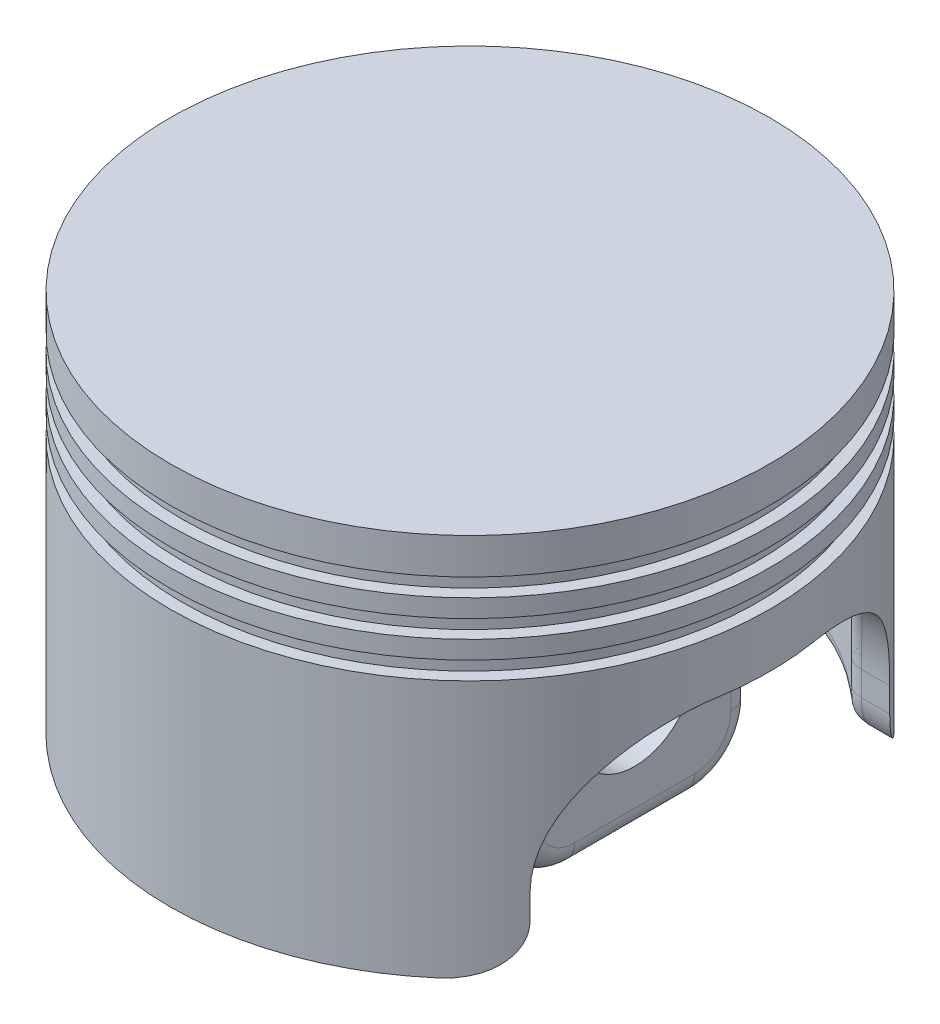
SolidWorks part; units mm, degrees
ref_plane "Front Plane" through (0, 0, 0) normal (0, 0, 1) x (1, 0, 0)
ref_plane "Top Plane" through (0, 0, 0) normal (0, 1, 0) x (1, 0, 0)
ref_plane "Right Plane" through (0, 0, 0) normal (1, 0, 0) x (0, 0, -1)
sketch "Sketch1" plane through (0, 0, 0) normal (1, 0, 0) x (0, 0, -1)
  line L0 (0, 0) -> (63.5, 0)
  line L4 (57.15, -19) -> (0, -19)
  line L5 (0, -19) -> (0, 0)
  line L6 (63.5, 0) -> (63.5, -81.28)
  line L7 (63.5, -81.28) -> (57.15, -81.28)
  line L8 (57.15, -81.28) -> (57.15, -19)
  dimension "D1" = 19
  dimension "D2" = 63.5
  dimension "D3" = 6.35
  dimension "D4" = 81.28
revolve "Revolve1" add sketch "Sketch1" angle 360 about L5
sketch "Sketch2" plane through (0, 0, 0) normal (0, 0, 1) x (1, 0, 0)
  line L0 (63.5, 0) -> (-63.5, 0) construction
  line L1 (63.5, -7.62) -> (60.96, -7.62)
  line L2 (63.5, -7.62) -> (63.5, -11.43)
  line L3 (63.5, -11.43) -> (60.96, -11.43)
  line L4 (60.96, -7.62) -> (60.96, -11.43)
  line L5 (63.5, -7.62) -> (60.96, -11.43) construction
  line L6 (63.5, -11.43) -> (60.96, -7.62) construction
  point P0 (62.23, -9.525)
  dimension "D1" = 7.62
  dimension "D2" = 3.81
  dimension "D3" = 2.54
  dimension "D4" = 63.5
ref_axis "Axis1" through (0, 4.064, 0) along (0, -1, 0)
revolve "Cut-Revolve1" cut sketch "Sketch2" angle 360 about axis through (0, 4.064, 0) along (0, -1, 0)
pattern_linear "LPattern1" count 3 spacing 7.62 along (0, -1, 0) of "Cut-Revolve1"
sketch "Sketch4" plane through (0, 0, 0) normal (1, 0, 0) x (0, 0, -1)
  line L0 (-57.15, -81.28) -> (57.15, -81.28) construction
  line L1 (-38.1, -38.1) -> (38.1, -38.1)
  line L2 (-38.1, -38.1) -> (-38.1, -81.28)
  line L3 (-38.1, -81.28) -> (38.1, -81.28)
  line L4 (38.1, -38.1) -> (38.1, -81.28)
  line L5 (-38.1, -38.1) -> (38.1, -81.28) construction
  line L6 (-38.1, -81.28) -> (38.1, -38.1) construction
  line L7 (63.5, 0) -> (-63.5, 0) construction
  point P0 (0, -59.69)
  dimension "D1" = 76.2
  dimension "D2" = 38.1
extrude "Cut-Extrude1" cut sketch "Sketch4" against normal mid plane 166
fillet "Fillet1" radius 28 4 edges at (-46.6985, -38.1, -38.1) (-46.6985, -38.1, 38.1) (46.6985, -38.1, -38.1) (46.6985, -38.1, 38.1)
sketch "Sketch5" plane through (0, -19, 0) normal (0, -1, 0) x (1, 0, 0)
  line L1 (-34.88, 25.4) -> (-15.88, 25.4)
  line L2 (-34.88, 25.4) -> (-34.88, -25.4)
  line L3 (-34.88, -25.4) -> (-15.88, -25.4)
  line L4 (-15.88, 25.4) -> (-15.88, -25.4)
  line L5 (-34.88, 25.4) -> (-15.88, -25.4) construction
  line L6 (-34.88, -25.4) -> (-15.88, 25.4) construction
  point P0 (-25.38, 0)
  dimension "D1" = 15.88
  dimension "D2" = 50.8
  dimension "D3" = 19
extrude "Boss-Extrude1" add sketch "Sketch5" along normal blind 63.5
mirror "Mirror1" about plane through (0, 0, 0) normal (1, 0, 0) of "Boss-Extrude1"
sketch "Sketch6" plane through (-34.88, 0, 0) normal (-1, 0, 0) x (0, 0, 1)
  line L0 (25.4, -82.5) -> (-25.4, -82.5) construction
  circle A0 centre (0, -57.1) radius 12.7
  dimension "D1" = 25.4
  dimension "D2" = 25.4
extrude "Cut-Extrude2" cut sketch "Sketch6" against normal blind 127.5
fillet "Fillet3" radius 12.7 4 edges at (-25.38, -82.5, -25.4) (-25.38, -82.5, 25.4) (25.38, -82.5, -25.4) (25.38, -82.5, 25.4)
fillet "Fillet4" radius 10 4 edges at (46.6985, -81.28, -38.1) (46.6985, -81.28, 38.1) (-46.6985, -81.28, -38.1) (-46.6985, -81.28, 38.1)
fillet "Fillet5" radius 5 20 edges at (34.88, -44.4, 25.4) (34.88, -78.7803, 21.6803) (34.88, -44.4, -25.4) (34.88, -78.7803, -21.6803) (15.88, -44.4, -25.4) (15.88, -78.7803, -21.6803) (15.88, -44.4, 25.4) (15.88, -78.7803, 21.6803) (-15.88, -44.4, -25.4) (-15.88, -78.7803, -21.6803) (-15.88, -44.4, 25.4) (-15.88, -78.7803, 21.6803) (-34.88, -44.4, 25.4) (-34.88, -78.7803, 21.6803) (-34.88, -44.4, -25.4) (-34.88, -78.7803, -21.6803) (34.88, -82.5, 0) (15.88, -82.5, 0) (-15.88, -82.5, 0) (-34.88, -82.5, 0)
fillet "Fillet6" radius 5 1 edges at (0, -19, -57.15)
fillet "Fillet7" radius 5 16 edges at (41.3657, -76.2692, 39.4335) (42.5971, -68.69, 38.1) (50.4318, -43.6881, 26.8841) (57.15, -38.1, 0) (46.055, -51.2516, -33.8387) (42.5971, -68.69, -38.1) (40.0022, -78.1316, -40.816) (0, -81.28, -57.15) (-41.3657, -76.2692, -39.4335) (-42.5971, -68.69, -38.1) (-50.4318, -43.6881, -26.8841) (-57.15, -38.1, 0) (-46.055, -51.2516, 33.8387) (-42.5971, -68.69, 38.1) (-40.0022, -78.1316, 40.816) (0, -81.28, 57.15)
